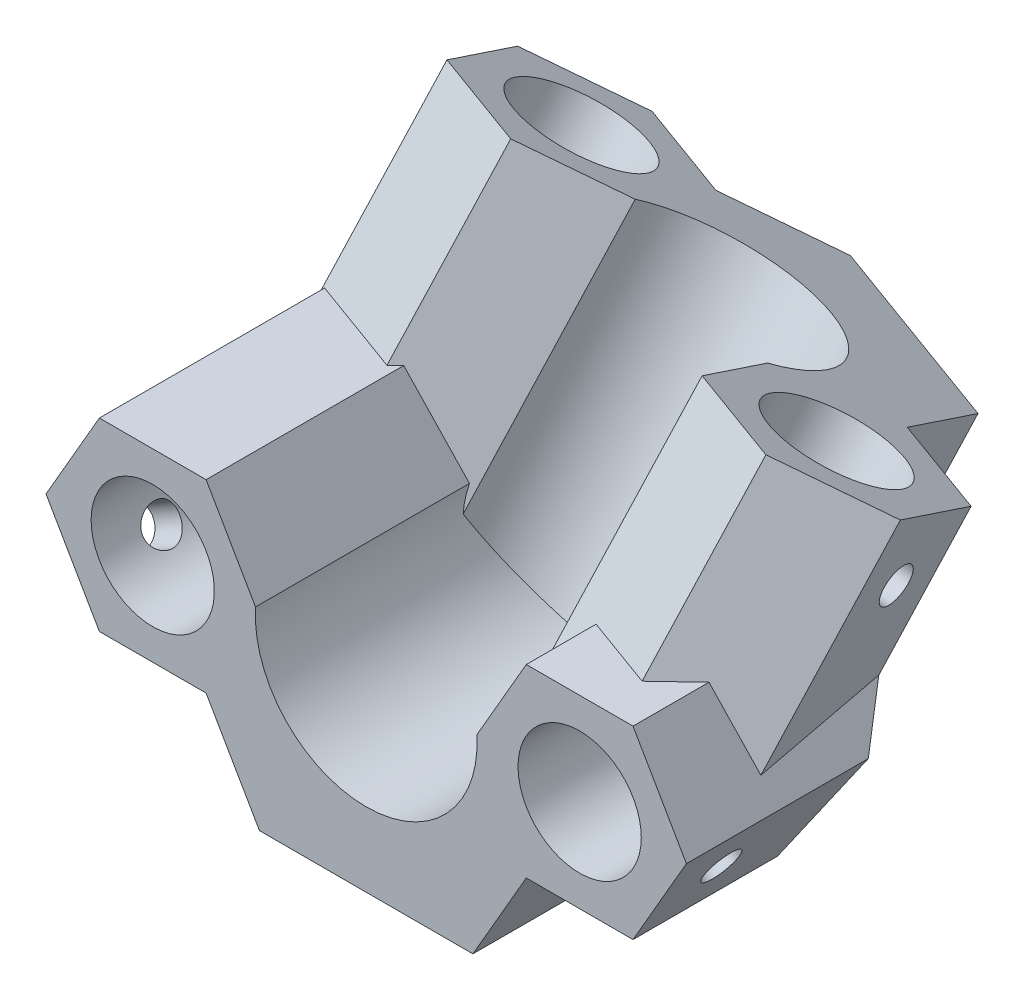
SolidWorks part; units mm, degrees
ref_plane "Front Plane" through (0, 0, 0) normal (0, 0, 1) x (1, 0, 0)
ref_plane "Top Plane" through (0, 0, 0) normal (0, 1, 0) x (1, 0, 0)
ref_plane "Right Plane" through (0, 0, 0) normal (1, 0, 0) x (0, 0, -1)
sketch "Sketch2" plane through (0, 0, 0) normal (0, 1, 0) x (1, 0, 0)
  line L0 (0, 0) -> (0, -10) construction
  line L1 (0, 0) -> (3.4202, 9.3969) construction
  dimension "D1" = 10
  dimension "D2" = 10
  dimension "D3" = 160
ref_plane "Plane1" through (0, 0, 0) normal (0.9397, 0, 0.342) x (0.342, 0, -0.9397)
sketch "Sketch3" plane through (0, 0, 0) normal (0.9397, 0, 0.342) x (0.342, 0, -0.9397)
  line L0 (0, 0) -> (10, 17.3205) construction
  line L1 (10, 17.3205) -> (10, 0) construction
  line L2 (10, 0) -> (0, 0) construction
  dimension "D1" = 30
  dimension "D2" = 10
sketch "Sketch5" plane through (0, 0, 0) normal (0, 0, 1) x (1, 0, 0)
  line L0 (0, 0) -> (8.6603, 0) construction
  line L1 (14.8205, 4.3301) -> (8.6603, 15)
  line L2 (8.6603, 15) -> (-8.6603, 15)
  line L3 (-8.6603, 15) -> (-12.9904, 7.5)
  line L4 (-12.9904, -7.5) -> (-8.6603, -15)
  line L5 (-8.6603, -15) -> (8.6603, -15)
  line L6 (8.6603, -15) -> (12.9904, -7.5)
  line L7 (0, -13.4183) -> (0, 13.4183) construction
  line L8 (25.9808, 0) -> (21.6506, 7.5)
  line L9 (21.6506, 7.5) -> (12.9904, 7.5)
  line L10 (12.9904, 7.5) -> (8.9827, 0.5584)
  line L11 (8.6603, 0) -> (8.9827, -0.5584) construction
  line L12 (12.9904, -7.5) -> (21.6506, -7.5)
  line L13 (21.6506, -7.5) -> (25.9808, 0)
  line L14 (-21.6506, -7.5) -> (-25.9808, 0)
  line L15 (-12.9904, -7.5) -> (-21.6506, -7.5)
  line L16 (-8.9827, -0.5584) -> (-12.9904, -7.5) construction
  line L17 (-12.9904, 7.5) -> (-8.9827, 0.5584)
  line L18 (-21.6506, 7.5) -> (-12.9904, 7.5)
  line L19 (-25.9808, 0) -> (-21.6506, 7.5)
  line L20 (-12.9904, 7.5) -> (-14.8205, 4.3301) construction
  line L21 (-14.8205, 4.3301) -> (-17.3205, 0) construction
  line L22 (-17.3205, 0) -> (-14.8205, -4.3301) construction
  line L23 (-14.8205, -4.3301) -> (-12.9904, -7.5) construction
  line L24 (-8.9827, 0.5584) -> (-8.6603, 0) construction
  line L25 (-8.6603, 0) -> (-8.9827, -0.5584) construction
  line L26 (10.8253, -3.75) -> (12.9904, -7.5) construction
  line L27 (12.9904, -7.5) -> (13.5705, -6.4952) construction
  line L28 (14.8205, -4.3301) -> (17.3205, 0) construction
  line L29 (13.5705, -6.4952) -> (14.8205, -4.3301) construction
  line L30 (8.9827, -0.5584) -> (10.8253, -3.75) construction
  line L31 (8.9827, 0.5584) -> (8.6603, 0) construction
  line L32 (8.6603, 0) -> (9, 0) construction
  line L33 (9, 0) -> (15, 0) construction
  line L34 (15, 0) -> (17.3205, 0) construction
  line L35 (17.3205, 0) -> (14.8205, 4.3301) construction
  circle A0 centre (0, 0) radius 15 construction
  arc A1 (-8.9827, 0.5584) -> (8.9827, 0.5584) centre (0, 0) ccw
  circle A2 centre (17.3205, 0) radius 7.5 construction
  circle A3 centre (17.3205, 0) radius 5
  circle A4 centre (-17.3205, 0) radius 5
  arc A5 (8.9827, 0.5584) -> (-8.9827, 0.5584) centre (0, 0) ccw construction
  dimension "D2" = 18
  dimension "D4" = 10
  dimension "D1" = 30
  dimension "D3" = 15
extrude "Boss-Extrude2" add sketch "Sketch5" along normal blind 15 contours A4 | L17 A1 L10 L9 L8 L13 L12 L6 L5 L4 L15 L14 L19 L18 | A3
ref_plane "Plane2" through (3.4202, 17.3205, -9.3969) normal (0.171, 0.866, -0.4698) x (0.9853, -0.1503, 0.0815)
sketch "Sketch10" plane through (0, 0, 0) normal (0, 0, -1) x (-1, 0, 0)
  line L0 (-8.9827, 0.5584) -> (-12.9904, 7.5)
  line L1 (-12.9904, 7.5) -> (-21.6506, 7.5)
  line L2 (-21.6506, 7.5) -> (-25.9808, 0)
  line L3 (-25.9808, 0) -> (-21.6506, -7.5)
  line L4 (-21.6506, -7.5) -> (-12.9904, -7.5)
  line L5 (-12.9904, -7.5) -> (-8.6603, -15)
  line L6 (-8.6603, -15) -> (8.6603, -15)
  line L7 (8.6603, -15) -> (12.9904, -7.5)
  line L8 (12.9904, -7.5) -> (21.6506, -7.5)
  line L9 (21.6506, -7.5) -> (25.9808, 0)
  line L10 (25.9808, 0) -> (21.6506, 7.5)
  line L11 (21.6506, 7.5) -> (12.9904, 7.5)
  line L12 (21.6506, 7.5) -> (12.9904, 7.5) construction
  line L13 (12.9904, 7.5) -> (8.9827, 0.5584)
  arc A0 (-8.9827, 0.5584) -> (8.9827, 0.5584) centre (0, 0) ccw
  arc A1 (-8.9827, 0.5584) -> (8.9827, 0.5584) centre (0, 0) ccw construction
  arc A2 (8.9827, 0.5584) -> (-8.9827, 0.5584) centre (0, 0) ccw construction
sketch "Sketch6" plane through (3.4202, 17.3205, -9.3969) normal (0.171, 0.866, -0.4698) x (0.9853, -0.1503, 0.0815)
  line L0 (-4.5094, -14.3061) -> (4.5094, 14.3061) construction
  line L1 (-3.7502, 16.9096) -> (-10.1348, 11.0583)
  line L2 (-15.4367, 0.3256) -> (-14.6442, -3.2478)
  line L3 (-12.769, -11.7026) -> (-4.5094, -14.3061) construction
  line L4 (10.1348, -11.0583) -> (10.9901, -10.2744) construction
  line L5 (14.6442, 3.2478) -> (12.769, 11.7026)
  line L6 (12.769, 11.7026) -> (-3.7502, 16.9096)
  line L7 (2.6035, 8.2596) -> (0, 0) construction
  line L8 (-14.3061, 4.5094) -> (16.5193, -5.207) construction
  line L9 (3.7502, -16.9096) -> (10.1348, -11.0583) construction
  line L10 (24.7789, -7.8105) -> (22.9038, 0.6443)
  line L11 (22.9038, 0.6443) -> (14.6442, 3.2478)
  line L12 (14.6442, 3.2478) -> (11.4519, 0.3222) construction
  line L13 (8.3993, -3.233) -> (10.1348, -11.0583)
  line L14 (10.1348, -11.0583) -> (18.3944, -13.6618)
  line L15 (18.3944, -13.6618) -> (24.7789, -7.8105)
  line L16 (-24.7789, 7.8105) -> (-22.9038, -0.6443)
  line L17 (-22.9038, -0.6443) -> (-14.6442, -3.2478)
  line L18 (-14.6442, -3.2478) -> (-8.735, 2.1678)
  line L19 (-9.1972, 6.8309) -> (-10.1348, 11.0583) construction
  line L20 (-10.1348, 11.0583) -> (-18.3944, 13.6618)
  line L21 (-18.3944, 13.6618) -> (-24.7789, 7.8105)
  line L22 (-4.5094, -14.3061) -> (3.7502, -16.9096) construction
  line L23 (-14.6442, -3.2478) -> (-12.769, -11.7026) construction
  line L24 (-8.735, 2.1678) -> (-8.2596, 2.6035) construction
  line L25 (-8.2596, 2.6035) -> (-8.3993, 3.233) construction
  line L26 (-8.3993, 3.233) -> (-9.1972, 6.8309) construction
  line L27 (-10.1348, 11.0583) -> (-10.9901, 10.2744) construction
  line L28 (-12.8332, 8.5853) -> (-16.5193, 5.207) construction
  line L29 (-10.9901, 10.2744) -> (-12.8332, 8.5853) construction
  line L30 (-16.5193, 5.207) -> (-14.3061, 4.5094) construction
  line L31 (-16.5193, 5.207) -> (-15.4367, 0.3256) construction
  line L32 (8.2596, -2.6035) -> (8.3993, -3.233) construction
  line L33 (8.735, -2.1678) -> (8.2596, -2.6035) construction
  line L34 (11.4519, 0.3222) -> (8.735, -2.1678) construction
  line L35 (16.5193, -5.207) -> (15.4367, -0.3256) construction
  line L36 (15.4367, -0.3256) -> (14.8954, 2.1151) construction
  line L37 (14.8954, 2.1151) -> (14.6442, 3.2478) construction
  line L38 (12.8332, -8.5853) -> (16.5193, -5.207) construction
  line L39 (10.9901, -10.2744) -> (12.8332, -8.5853) construction
  circle A0 centre (0, 0) radius 15 construction
  arc A1 (8.3993, -3.233) -> (-8.735, 2.1678) centre (0, 0) ccw
  circle A2 centre (16.5193, -5.207) radius 7.5 construction
  circle A3 centre (16.5193, -5.207) radius 5
  circle A4 centre (-16.5193, 5.207) radius 7.5 construction
  circle A5 centre (-16.5193, 5.207) radius 5
  arc A6 (-2.7056, -8.5837) -> (8.3993, -3.233) centre (0, 0) ccw construction
  arc A7 (-8.735, 2.1678) -> (-2.7056, -8.5837) centre (0, 0) ccw construction
  dimension "D2" = 18
  dimension "D3" = 10
  dimension "D5" = 10
  dimension "D1" = 30
  dimension "D4" = 15
  dimension "D6" = 15
extrude "Boss-Extrude3" add sketch "Sketch6" against normal up to surface (37.3205 mm away) contours L18 A1 L13 L14 L15 L10 L11 L5 L6 L1 L20 L21 L16 L17 | A5 | A3 up to face at (0, -15, 7.5)
sketch "Sketch7" plane through (0, 0, 15) normal (0, 0, 1) x (1, 0, 0)
  circle A0 centre (-17.3205, 0) radius 5
  circle A1 centre (-17.3205, 0) radius 5 construction
  circle A2 centre (0, 0) radius 9
  arc A3 (-8.9827, 0.5584) -> (8.9827, 0.5584) centre (0, 0) ccw construction
  circle A4 centre (17.3205, 0) radius 5
  arc A5 (19.6231, -4.4382) -> (12.6933, -1.8945) centre (17.3205, 0) ccw construction
extrude "Cut-Extrude1" cut sketch "Sketch7" against normal up to surface (15 mm away) up to face at (-13.56, -1.3492, 0)
sketch "Sketch8" plane through (0, 0, 0) normal (0, 1, 0) x (1, 0, 0)
  line L0 (-25.9808, -15) -> (25.9808, -15)
  line L1 (25.9808, -15) -> (25.9808, -23.6809)
  line L2 (25.9808, -23.6809) -> (-25.9808, -23.6809)
  line L3 (-25.9808, -23.6809) -> (-25.9808, -15)
extrude "Cut-Extrude2" cut sketch "Sketch8" against normal through all both and the other way through all
sketch "Sketch9" plane through (0, 0, 15) normal (0, 0, 1) x (1, 0, 0)
  line L0 (-8.6603, -15) -> (-12.9904, -7.5)
  line L1 (-12.9904, -7.5) -> (-21.6506, -7.5)
  line L2 (-21.6506, -7.5) -> (-25.9808, 0)
  line L3 (-25.9808, 0) -> (-27.3759, -15)
  line L4 (-27.3759, -15) -> (-8.6603, -15)
  line L5 (8.6603, -15) -> (12.9904, -7.5)
  line L6 (12.9904, -7.5) -> (21.6506, -7.5)
  line L7 (21.6506, -7.5) -> (25.9808, 0)
  line L8 (25.9808, 0) -> (21.219, -15)
  line L9 (21.219, -15) -> (8.6603, -15)
extrude "Cut-Extrude3" cut sketch "Sketch9" against normal through all both and the other way through all
extrude "Boss-Extrude4" add sketch "Sketch10" along normal up to surface (15.5058 mm away) up to face at (6.3157, -3.7874, -13.8064)
sketch "Sketch11" plane through (3.4202, 17.3205, -9.3969) normal (0.171, 0.866, -0.4698) x (0.9853, -0.1503, 0.0815)
  line L0 (-3.7502, 16.9096) -> (-10.1348, 11.0583)
  line L1 (-10.1348, 11.0583) -> (-18.3944, 13.6618)
  line L2 (-18.3944, 13.6618) -> (-26.2017, 6.5066)
  line L3 (-24.3748, -13.1846) -> (-27.8723, 24.5131) construction
  line L4 (-26.2017, 6.5066) -> (-27.8723, 24.5131)
  line L5 (-27.8723, 24.5131) -> (-3.7502, 16.9096)
  line L6 (12.769, 11.7026) -> (14.6442, 3.2478)
  line L7 (14.6442, 3.2478) -> (25.6176, -0.2111)
  line L8 (26.8213, -13.1846) -> (24.8661, 7.8896) construction
  line L9 (25.6176, -0.2111) -> (24.8661, 7.8896)
  line L10 (24.8661, 7.8896) -> (12.769, 11.7026)
extrude "Cut-Extrude4" cut sketch "Sketch11" against normal through all both and the other way through all
sketch "Sketch12" plane through (-19.4856, -11.25, 0) normal (-0.866, -0.5, 0) x (0, 0, 1)
  line L0 (15, 8.6603) -> (-8.119, 8.6603) construction
  line L1 (15, 4.3301) -> (15, 12.9904) construction
  line L2 (-8.8355, 4.3301) -> (-7.4025, 12.9904) construction
  circle A0 centre (10, 8.6603) radius 1.5
  dimension "D1" = 3
  dimension "D2" = 5
extrude "Cut-Extrude5" cut sketch "Sketch12" against normal up to surface and the other way through all up to face at (-22.3205, 0, 15)
sketch "Sketch13" plane through (19.4856, -11.25, 0) normal (0.866, -0.5, 0) x (0, 0, -1)
  line L0 (-15, 8.6603) -> (-1.7562, 8.6603) construction
  line L1 (-15, 4.3301) -> (-15, 12.9904) construction
  line L2 (-3.2722, 4.3301) -> (-0.2402, 12.9904) construction
  circle A0 centre (-10, 8.6603) radius 1.5
  dimension "D1" = 3
  dimension "D2" = 5
extrude "Cut-Extrude6" cut sketch "Sketch13" against normal up to surface (2.7303 mm away) contours A0 up to face at (17.3205, 0, 0.3293)
sketch "Sketch14" plane through (21.6427, -5.625, -2.4908) normal (0.9619, -0.25, -0.1107) x (-0.1071, 0.0278, -0.9939)
  line L0 (1.8237, 21.7181) -> (-5.114, 8.7865) construction
  line L1 (-1.992, 23.7651) -> (5.6394, 19.671) construction
  line L2 (0.1152, 9.3741) -> (-10.3432, 8.1988) construction
  circle A0 centre (-0.5401, 17.3121) radius 1.5
  dimension "D1" = 3
  dimension "D2" = 5
extrude "Cut-Extrude7" cut sketch "Sketch14" against normal up to surface (2.5505 mm away) up to face at (19.6962, 19.7049, 0.9219)
sketch "Sketch15" plane through (-14.9782, -5.625, -15.8197) normal (-0.6657, -0.25, -0.7031) x (-0.7462, 0.223, 0.6272)
  line L0 (3.8464, 21.4524) -> (9.6694, -3.2805) construction
  line L1 (-0.3685, 20.4601) -> (8.0613, 22.4447) construction
  line L2 (8.9416, -4.1065) -> (14.7444, 2.48) construction
  circle A0 centre (4.9923, 16.5855) radius 1.5
  dimension "D1" = 3
  dimension "D2" = 5
extrude "Cut-Extrude8" cut sketch "Sketch15" against normal up to surface (2.6834 mm away) contours A0 up to face at (-12.8558, 19.7049, -10.926)
sketch "Sketch16" plane through (4.443, -7.5, -12.207) normal (0.2962, -0.5, -0.8138) x (-0.9551, -0.1551, -0.2524)
  line L0 (-3.5809, 19.6768) -> (1.5506, -8.5203) construction
  line L1 (-12.1012, 18.1262) -> (4.9394, 21.2274) construction
  line L2 (10.0709, -6.9697) -> (-4.4154, -9.606) construction
  line L3 (-0.909, -8.9679) -> (-2.3414, -1.0972)
  line L4 (-2.3414, -1.0972) -> (2.5778, -0.202)
  line L5 (2.5778, -0.202) -> (4.0102, -8.0727)
  line L6 (4.0102, -8.0727) -> (-0.909, -8.9679)
  point P8 (0.1182, -0.6496)
  dimension "D1" = 5
  dimension "D2" = 8
extrude "Boss-Extrude5" add sketch "Sketch16" along normal blind 5
sketch "Sketch17" plane through (2.3492, 0, 0.8551) normal (0.9397, 0, 0.342) x (0.342, 0, -0.9397)
  line L0 (14.8253, -9.3218) -> (10.8253, -16.25) construction
  line L1 (16.9904, -10.5718) -> (12.6603, -8.0718) construction
  line L2 (12.9904, -17.5) -> (8.6603, -15) construction
  circle A0 centre (12.8253, -12.7859) radius 1.5
  dimension "D1" = 3
extrude "Cut-Extrude9" cut sketch "Sketch17" against normal through all
fillet "Fillet1" radius 3 1 edges at (5.8111, -10.5718, -15.9657) type face fillet first side face at (5.0706, -9.3218, -13.9312) second side face at (5.127, -14.0359, -14.0864)
fillet "Fillet2" radius 3 1 edges at (4.443, -17.5, -12.207) type face fillet first side face at (4.8705, -15.3349, -13.3816) second side face at (3.7025, -16.25, -10.1725)
